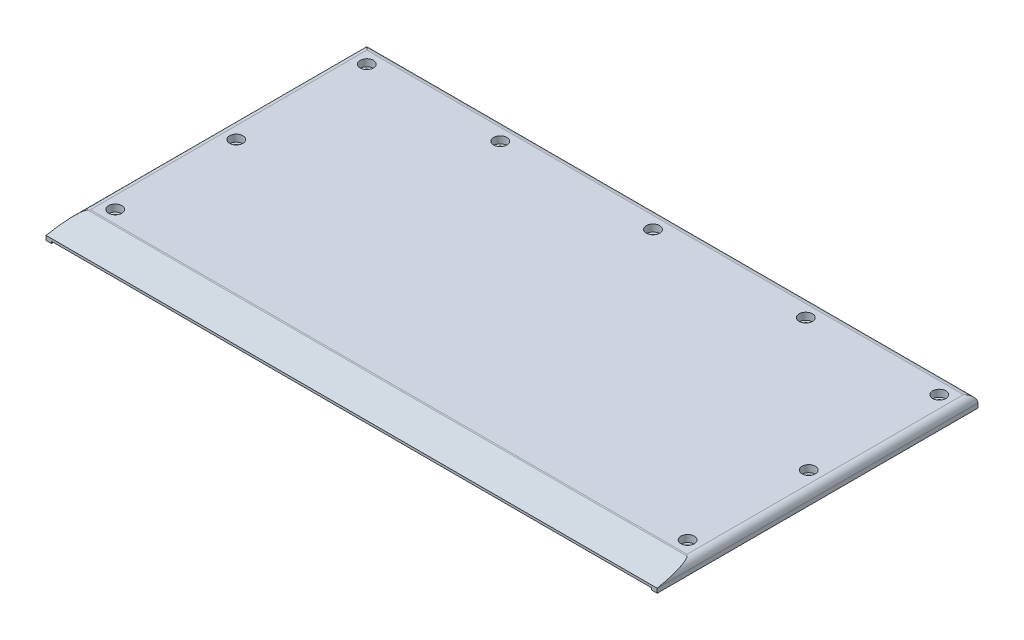
SolidWorks part; units mm, degrees
ref_plane "Front Plane" through (0, 0, 0) normal (0, 0, 1) x (1, 0, 0)
ref_plane "Top Plane" through (0, 0, 0) normal (0, 1, 0) x (1, 0, 0)
ref_plane "Right Plane" through (0, 0, 0) normal (1, 0, 0) x (0, 0, -1)
sketch "Sketch1" plane through (0, 0, 0) normal (0, 1, 0) x (1, 0, 0)
  line L1 (0, 0) -> (252.42, 0)
  line L2 (0, 0) -> (0, -132.49)
  line L3 (0, -132.49) -> (252.42, -132.49)
  line L4 (252.42, 0) -> (252.42, -132.49)
  line L5 (0, -132.49) -> (2.3, -132.49)
  line L6 (0, -132.49) -> (0, 0)
  line L7 (0, 0) -> (2.3, 0)
  line L8 (2.3, -132.49) -> (2.3, 0)
  line L9 (252.42, -132.49) -> (250.12, -132.49)
  line L10 (252.42, -132.49) -> (252.42, 0)
  line L11 (252.42, 0) -> (250.12, 0)
  line L12 (250.12, -132.49) -> (250.12, 0)
  line L13 (250.12, 0) -> (2.3, 0)
  line L14 (250.12, 0) -> (250.12, -1.8)
  line L15 (250.12, -1.8) -> (2.3, -1.8)
  line L16 (2.3, 0) -> (2.3, -1.8)
  line L17 (2.3, -132.49) -> (250.12, -132.49)
  line L18 (2.3, -132.49) -> (2.3, -121.92)
  line L19 (2.3, -121.92) -> (250.12, -121.92)
  line L20 (250.12, -132.49) -> (250.12, -121.92)
  circle A0 centre (8, -111.92) radius 1.6
  circle A1 centre (8, -61.92) radius 1.6
  circle A2 centre (8, -8) radius 1.6
  circle A3 centre (244.42, -8) radius 1.6
  circle A4 centre (244.42, -61.92) radius 1.6
  circle A5 centre (244.42, -111.92) radius 1.6
  circle A6 centre (63.11, -8) radius 1.6
  circle A7 centre (126.21, -8) radius 1.6
  circle A8 centre (189.31, -8) radius 1.6
  dimension "D3" = 3.2
  dimension "D4" = 3.2
  dimension "D5" = 3.2
  dimension "D6" = 3.2
  dimension "D7" = 3.2
  dimension "D8" = 3.2
  dimension "D9" = 3.2
  dimension "D10" = 3.2
  dimension "D20" = 3.2
  dimension "D1" = 252.42
  dimension "D2" = 132.49
  dimension "D11" = 1.8
  dimension "D12" = 2.3
  dimension "D13" = 2.3
  dimension "D14" = 8
  dimension "D15" = 8
  dimension "D16" = 8
  dimension "D17" = 63.11
  dimension "D18" = 63.11
  dimension "D19" = 126.21
  dimension "D21" = 61.92
  dimension "D22" = 111.92
  dimension "D23" = 10.57
extrude "Boss-Extrude1" add sketch "Sketch1" along normal blind 4 contours L8 L19 L12 L15 A8 A7 A6 A5 A4 A3 A2 A1 A0 | L12 L3 L4 L1 | L19 L8 L3 L12 | L3 L8 L1 L2 | L15 L12 L1 L8 region at (1.15, 0, 66.245) region at (126.21, 0, 0.9) region at (251.27, 0, 66.245) region at (126.21, 0, 61.9058) region at (126.21, 0, 127.205)
extrude "Boss-Extrude2" add sketch "Sketch1<5>" against normal blind 0.8 contours L3 L8 L1 L2 | L15 L12 L1 L8 | L12 L3 L4 L1 region at (1.15, 0, 66.245) region at (126.21, 0, 0.9) region at (251.27, 0, 66.245)
sketch "Sketch1<5>" plane through (0, 0, 0) normal (0, 1, 0) x (1, 0, 0) same geometry as "Sketch1"
extrude "Boss-Extrude3" add sketch "Sketch1<6>" along normal blind 1.4 contours L19 L8 L3 L12 region at (126.21, 0, 127.205)
sketch "Sketch1<6>" plane through (0, 0, 0) normal (0, 1, 0) x (1, 0, 0) same geometry as "Sketch1"
sketch "Sketch2" plane through (0, 4, 0) normal (0, 1, 0) x (1, 0, 0)
  circle A0 centre (8, -8) radius 2.75
  circle A1 centre (63.11, -8) radius 2.75
  circle A2 centre (126.21, -8) radius 2.75
  circle A3 centre (189.31, -8) radius 2.75
  circle A4 centre (244.42, -8) radius 2.75
  circle A5 centre (244.42, -61.92) radius 2.75
  circle A6 centre (244.42, -111.92) radius 2.75
  circle A7 centre (8, -111.92) radius 2.75
  circle A8 centre (8, -61.92) radius 2.75
  dimension "D1" = 5.5
  dimension "D2" = 5.5
  dimension "D3" = 5.5
  dimension "D4" = 5.5
  dimension "D5" = 5.5
  dimension "D6" = 5.5
  dimension "D7" = 5.5
  dimension "D8" = 5.5
  dimension "D9" = 5.5
extrude "Cut-Extrude1" cut sketch "Sketch2" against normal blind 2.9
sketch "Sketch3" plane through (0, 0, 0) normal (-1, 0, 0) x (0, 0, 1)
  line L0 (117.49, 4) -> (132.49, 1)
  line L1 (0, 4) -> (132.49, 4) construction
  line L3 (132.49, 1) -> (132.49, 4)
  line L4 (132.49, 4) -> (117.49, 4)
  line L5 (132.49, 4) -> (132.49, -0.8) construction
  line L6 (0, -0.8) -> (132.49, -0.8) construction
  dimension "D1" = 15
  dimension "D2" = 1.8
extrude "Cut-Extrude2" cut sketch "Sketch3" against normal up to next
fillet "Fillet1" radius 3 4 edges at (0, 4, 58.745) (126.21, 4, 0) (126.21, 4, 117.49) (252.42, 4, 58.745)
